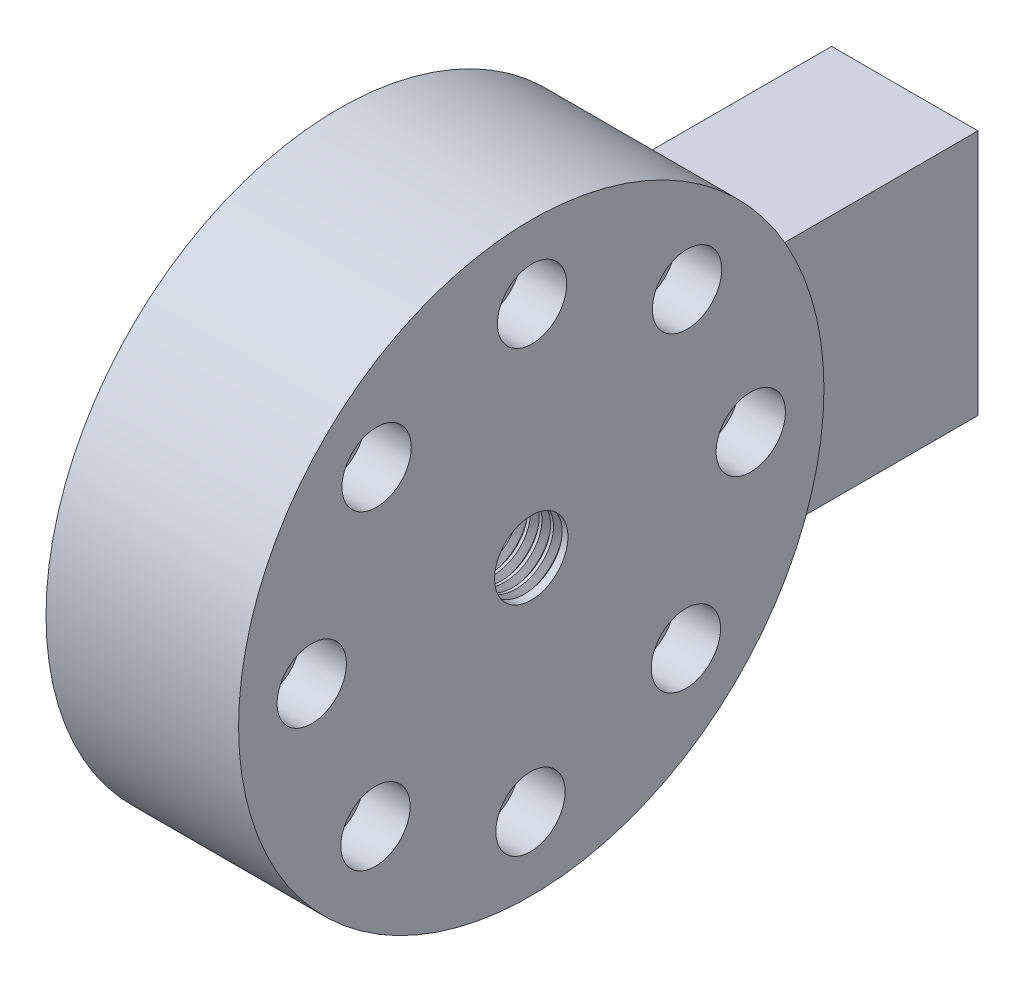
SolidWorks part; units mm, degrees
ref_plane "Front Plane" through (0, 0, 0) normal (0, 0, 1) x (1, 0, 0)
ref_plane "Top Plane" through (0, 0, 0) normal (0, 1, 0) x (1, 0, 0)
ref_plane "Right Plane" through (0, 0, 0) normal (1, 0, 0) x (0, 0, -1)
sketch "Sketch1" plane through (0, 0, 0) normal (1, 0, 0) x (0, 0, -1)
  circle A0 centre (0, 0) radius 38
  dimension "D1" = 76
extrude "Boss-Extrude1" add sketch "Sketch1" along normal blind 25
sketch "Sketch2" plane through (25, 0, 0) normal (1, 0, 0) x (0, 0, -1)
  circle A0 centre (0.1038, 28.4998) radius 3.5
  circle A2 centre (20.2258, 20.079) radius 3.5
  circle A3 centre (28.4998, -0.1038) radius 3.5
  circle A4 centre (20.079, -20.2258) radius 3.5
  circle A5 centre (-0.1038, -28.4998) radius 3.5
  circle A6 centre (-20.2258, -20.079) radius 3.5
  circle A7 centre (-28.4998, 0.1038) radius 3.5
  circle A8 centre (-20.079, 20.2258) radius 3.5
  circle A9 centre (0, 0) radius 28.5 construction
  dimension "D1" = 7
  dimension "D2" = 57
  dimension "D3" = 8
extrude "Cut-Extrude1" cut sketch "Sketch2" against normal blind 25 contours A0 | A2 | A3 | A4 | A5 | A6 | A7 | A8 | A8 region at (25, 28.4998, -0.1038) region at (25, 20.079, -20.2258) region at (25, -0.1038, -28.4998) region at (25, -20.2258, -20.079) region at (25, -28.4998, 0.1038) region at (25, -20.079, 20.2258) region at (25, 0.1038, 28.4998) region at (25, 20.2258, 20.079)
sketch "Sketch3" plane through (25, 0, 0) normal (1, 0, 0) x (0, 0, -1)
  circle A0 centre (0.1038, 28.4998) radius 4.5
  circle A1 centre (0, 0) radius 28.5 construction
  circle A2 centre (0, 0) radius 28.5 construction
  circle A3 centre (20.2258, 20.079) radius 4.5
  circle A4 centre (0, 0) radius 28.5 construction
  circle A5 centre (28.4998, -0.1038) radius 4.5
  circle A6 centre (0, 0) radius 28.5 construction
  circle A7 centre (20.079, -20.2258) radius 4.5
  circle A8 centre (0, 0) radius 28.5 construction
  circle A9 centre (-0.1038, -28.4998) radius 4.5
  circle A10 centre (0, 0) radius 28.5 construction
  circle A11 centre (-20.2258, -20.079) radius 4.5
  circle A12 centre (0, 0) radius 28.5 construction
  circle A13 centre (-28.4998, 0.1038) radius 4.5
  circle A14 centre (0, 0) radius 28.5 construction
  circle A15 centre (-20.079, 20.2258) radius 4.5
  dimension "D1" = 9
  dimension "D2" = 8
extrude "Cut-Extrude2" cut sketch "Sketch3" against normal blind 6
sketch "Sketch4" plane through (25, 0, 0) normal (1, 0, 0) x (0, 0, -1)
  circle A0 centre (0, 0) radius 4.7625
  dimension "D1" = 9.525
extrude "Cut-Extrude3" cut sketch "Sketch4" against normal through all contours A0
thread "Thread1" pitch 1.5 method cut profile "Thread Profile1" start angle 0, offset 0, length 0, pitch 1.5, diameter 9.525
ref_plane "Plane1" through (25, 0, 4.7625) normal (0, -1, 0) x (0, 0, 1)
sketch "Thread Profile1" plane through (25, 0, 4.7625) normal (0, -1, 0) x (0, 0, 1)
  line L0 (0, 0) -> (0, 1.5) construction
  line L1 (0, 0) -> (0.8119, 0.4687)
  line L2 (0.8119, 0.4687) -> (0.8119, 0.6562)
  line L3 (0.8119, 0.6562) -> (0, 1.125)
  line L4 (0.8119, 0.5625) -> (0, 0.5625) construction
  line L11 (0, 0) -> (0, 1.125)
  point P2 (0, 0)
  dimension "Pitch" = 1.5
  dimension "Profile_Angle" = 60
  dimension "Profile_Land" = 0.1875
  dimension "Profile_Height" = 0.8119
ref_plane "Plane2" through (0, 0, -38) normal (0, 0, 1) x (1, 0, 0)
sketch "Sketch8" plane through (0, 0, -38) normal (0, 0, 1) x (1, 0, 0)
  line L11 (0, 38) -> (0, -38) construction
  line L12 (3, 16) -> (22, 16)
  line L13 (3, 16) -> (3, -16)
  line L14 (3, -16) -> (22, -16)
  line L15 (22, 16) -> (22, -16)
  point P6 (3, 0)
  point P7 (0, 0)
  dimension "D1" = 3
  dimension "D2" = 19
  dimension "D3" = 32
extrude "Boss-Extrude2" add sketch "Sketch8" along normal up to surface and the other way blind 23 up to face at (25, 0, -38)
